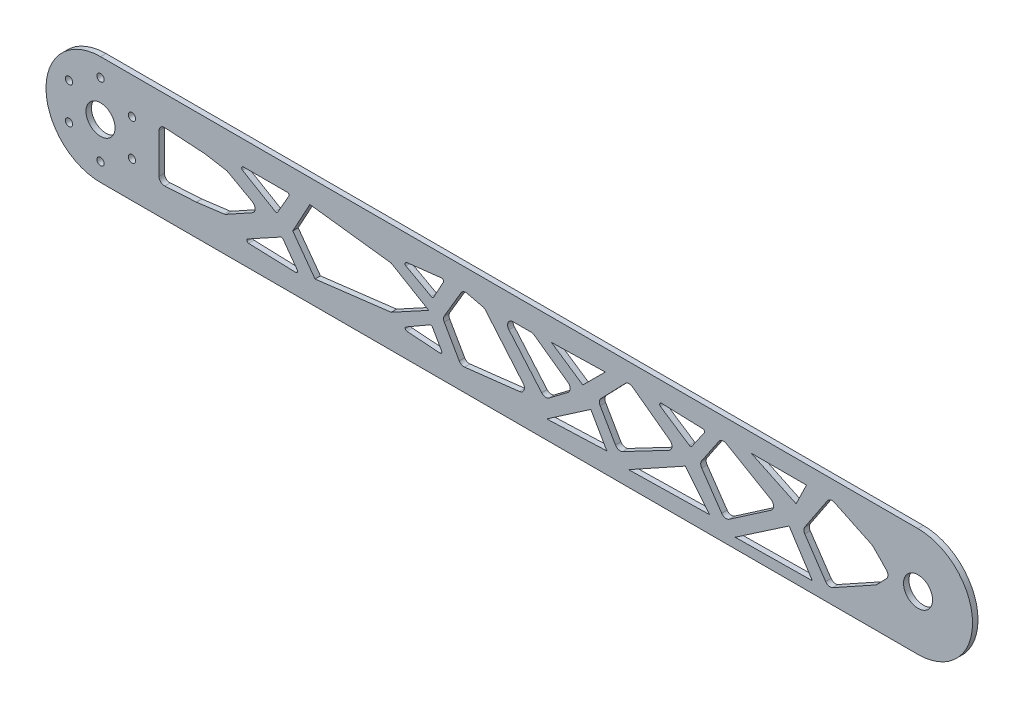
SolidWorks part; units mm, degrees
material "6061-T6 (SS)"
ref_plane "Front Plane" through (0, 0, 0) normal (0, 0, 1) x (1, 0, 0)
ref_plane "Top Plane" through (0, 0, 0) normal (0, 1, 0) x (1, 0, 0)
ref_plane "Right Plane" through (0, 0, 0) normal (1, 0, 0) x (0, 0, -1)
sketch "Sketch1" plane through (0, 0, 0) normal (0, 0, 1) x (1, 0, 0)
  line L0 (0, 0) -> (450, 0) construction
  line L1 (0, 30) -> (450, 30)
  line L2 (0, -30) -> (450, -30)
  arc A0 (0, 30) -> (0, -30) centre (0, 0) ccw
  arc A1 (450, -30) -> (450, 30) centre (450, 0) ccw
  circle A2 centre (0, 0) radius 20 construction
  circle A3 centre (0, 20) radius 2
  circle A4 centre (17.3205, 10) radius 2
  circle A5 centre (17.3205, -10) radius 2
  circle A6 centre (0, -20) radius 2
  circle A9 centre (0, 0) radius 8
  circle A10 centre (-17.3205, -10) radius 2
  circle A11 centre (-17.3205, 10) radius 2
  point P3 (225, 0)
  point P24 (0, 0)
  dimension "D1" = 30
  dimension "D3" = 40
  dimension "D4" = 4
  dimension "D6" = 16
  dimension "D2" = 450
  dimension "D5" = 6
extrude "Boss-Extrude1" add sketch "Sketch1" along normal blind 3
sketch "Sketch2" plane through (0, 0, 0) normal (0, 0, -1) x (-1, 0, 0)
  circle A0 centre (-450, 0) radius 8
  dimension "D1" = 16
extrude "Cut-Extrude1" cut sketch "Sketch2" against normal blind 10
sketch "Sketch3" plane through (0, 0, 0) normal (0, 0, -1) x (-1, 0, 0)
  line L0 (-225, 30) -> (-225, -30) construction
  line L1 (-450, 30) -> (0, 30) construction
  line L2 (0, -30) -> (-450, -30) construction
sketch "Sketch4" plane through (0, 0, 3) normal (0, 0, 1) x (1, 0, 0)
  line L3 (75.0512, 16.7519) -> (104.4964, 16.7519)
  line L4 (104.4964, 16.7519) -> (97.0103, 3.776)
  line L5 (97.0103, 3.776) -> (75.0512, 16.7519)
  line L6 (115.2364, 17.1336) -> (159.9949, 11.5901)
  line L7 (159.9949, 11.5901) -> (180.6552, -0.6182)
  line L8 (159.9949, -11.858) -> (118.0851, -16.9668)
  line L9 (118.0851, -16.9668) -> (105.8233, -0.1776)
  line L10 (105.8233, -0.1776) -> (115.2364, 17.1336)
  line L11 (189.6655, 18.5783) -> (182.9411, 6.2118)
  line L12 (189.6655, 18.5783) -> (165.3685, 15.767)
  line L13 (165.3685, 15.767) -> (182.9411, 6.2118)
  line L14 (199.5998, 18.5783) -> (188.3613, -0.4406)
  line L15 (188.3613, -0.4406) -> (198.4445, -18.0218)
  line L16 (198.4445, -18.0218) -> (236.2169, -13.6513)
  line L17 (236.2169, -13.6513) -> (211.3582, 15.767)
  line L18 (211.3582, 15.767) -> (199.5998, 18.5783)
  line L19 (220.5269, 17.1727) -> (237.9604, 17.1727)
  line L20 (237.9604, 17.1727) -> (260.5594, 1.0579)
  line L21 (244.6755, -10.9439) -> (220.5269, 17.1727)
  line L22 (265.4666, 6.2118) -> (277.8331, 18.5783)
  line L23 (277.8331, 18.5783) -> (248.2204, 17.8749)
  line L24 (248.2204, 17.8749) -> (265.4666, 6.2118)
  line L25 (165.3685, -16.3587) -> (182.2005, -6.7053)
  line L26 (182.2005, -6.7053) -> (188.6908, -18.0218)
  line L27 (188.6908, -18.0218) -> (165.3685, -16.3587)
  line L28 (245.6374, -19.8683) -> (269.8878, -3.2204)
  line L29 (269.8878, -3.2204) -> (278.7166, -18.6146)
  line L30 (278.7166, -18.6146) -> (245.6374, -19.8683)
  line L32 (290.6832, -21.5398) -> (321.9406, -4.2114)
  line L33 (321.9406, -4.2114) -> (335.2064, -20.704)
  line L34 (335.2064, -20.704) -> (290.6832, -21.5398)
  line L35 (341.9929, 19.1834) -> (329.7352, 1.0579)
  line L36 (329.7352, 1.0579) -> (343.6146, -19.1598)
  line L37 (343.6146, -19.1598) -> (373.065, 1.0579)
  line L38 (373.065, 1.0579) -> (341.9929, 19.1834)
  line L39 (244.6755, -10.9439) -> (260.5594, 1.0579)
  line L40 (273.8778, 3.1142) -> (290.6832, 20.5427)
  line L41 (290.6832, 20.5427) -> (317.2099, 1.0579)
  line L42 (317.2099, 1.0579) -> (284.8817, -15.8863)
  line L43 (284.8817, -15.8863) -> (273.8778, 3.1142)
  line L44 (305.3074, 19.271) -> (333.3759, 18.3243)
  line L45 (333.3759, 18.3243) -> (324.9421, 6.2118)
  line L46 (324.9421, 6.2118) -> (305.3074, 19.271)
  line L47 (358.198, 20.0502) -> (388.5975, 20.0502)
  line L48 (388.5975, 20.0502) -> (382.8865, 8.2928)
  line L49 (382.8865, 8.2928) -> (358.198, 20.0502)
  line L50 (349.331, -24.4281) -> (379.0302, -4.2114)
  line L51 (379.0302, -4.2114) -> (391.83, -23.927)
  line L52 (391.83, -23.927) -> (349.331, -24.4281)
  line L53 (386.543, -2.0485) -> (401.5864, 20.5696)
  line L54 (401.5864, 20.5696) -> (424.8813, 9.4759)
  line L55 (434.601, -0.4406) -> (424.8813, 9.4759)
  line L56 (434.601, -0.4406) -> (426.9833, -8.3408)
  line L57 (426.9833, -8.3408) -> (400.6645, -22.9126)
  line L58 (400.6645, -22.9126) -> (386.543, -2.0485)
  line L59 (159.9949, -11.858) -> (180.6552, -0.6182)
  line L60 (77.9082, -18.1131) -> (99.9591, -5.986)
  line L61 (99.9591, -5.986) -> (109.5177, -19.2166)
  line L62 (109.5177, -19.2166) -> (77.9082, -18.1131)
  line L63 (32.1814, 14.0452) -> (32.1814, -14.1865)
  line L64 (32.1814, -14.1865) -> (52.8225, -12.9556)
  line L65 (52.8225, -12.9556) -> (68.5544, -10.9439)
  line L66 (68.5544, -10.9439) -> (88.303, 0)
  line L67 (88.303, 0) -> (69.6625, 10.3469)
  line L68 (69.6625, 10.3469) -> (57.5717, 12.4236)
  line L69 (57.5717, 12.4236) -> (32.1814, 14.0452)
extrude "Cut-Extrude2" cut sketch "Sketch4" against normal blind 10
fillet "Fillet1" radius 3 7 edges at (57.5717, 12.4236, 1.5) (69.6625, 10.3469, 1.5) (88.303, 0, 1.5) (52.8225, -12.9556, 1.5) (68.5544, -10.9439, 1.5) (32.1814, -14.1865, 1.5) (32.1814, 14.0452, 1.5)
fillet "Fillet2" radius 1 15 edges at (324.9421, 6.2118, 1.5) (333.3759, 18.3243, 1.5) (305.3074, 19.271, 1.5) (189.6655, 18.5783, 1.5) (182.9411, 6.2118, 1.5) (165.3685, 15.767, 1.5) (182.2005, -6.7053, 1.5) (188.6908, -18.0218, 1.5) (165.3685, -16.3587, 1.5) (109.5177, -19.2166, 1.5) (99.9591, -5.986, 1.5) (77.9082, -18.1131, 1.5) (97.0103, 3.776, 1.5) (104.4964, 16.7519, 1.5) (75.0512, 16.7519, 1.5)
fillet "Fillet3" radius 3 23 edges at (400.6645, -22.9126, 1.5) (401.5864, 20.5696, 1.5) (260.5594, 1.0579, 1.5) (220.5269, 17.1727, 1.5) (244.6755, -10.9439, 1.5) (343.6146, -19.1598, 1.5) (284.8817, -15.8863, 1.5) (317.2099, 1.0579, 1.5) (236.2169, -13.6513, 1.5) (237.9604, 17.1727, 1.5) (211.3582, 15.767, 1.5) (199.5998, 18.5783, 1.5) (341.9929, 19.1834, 1.5) (290.6832, 20.5427, 1.5) (198.4445, -18.0218, 1.5) (188.3613, -0.4406, 1.5) (273.8778, 3.1142, 1.5) (329.7352, 1.0579, 1.5) (386.543, -2.0485, 1.5) (424.8813, 9.4759, 1.5) (426.9833, -8.3408, 1.5) (434.601, -0.4406, 1.5) (373.065, 1.0579, 1.5)
